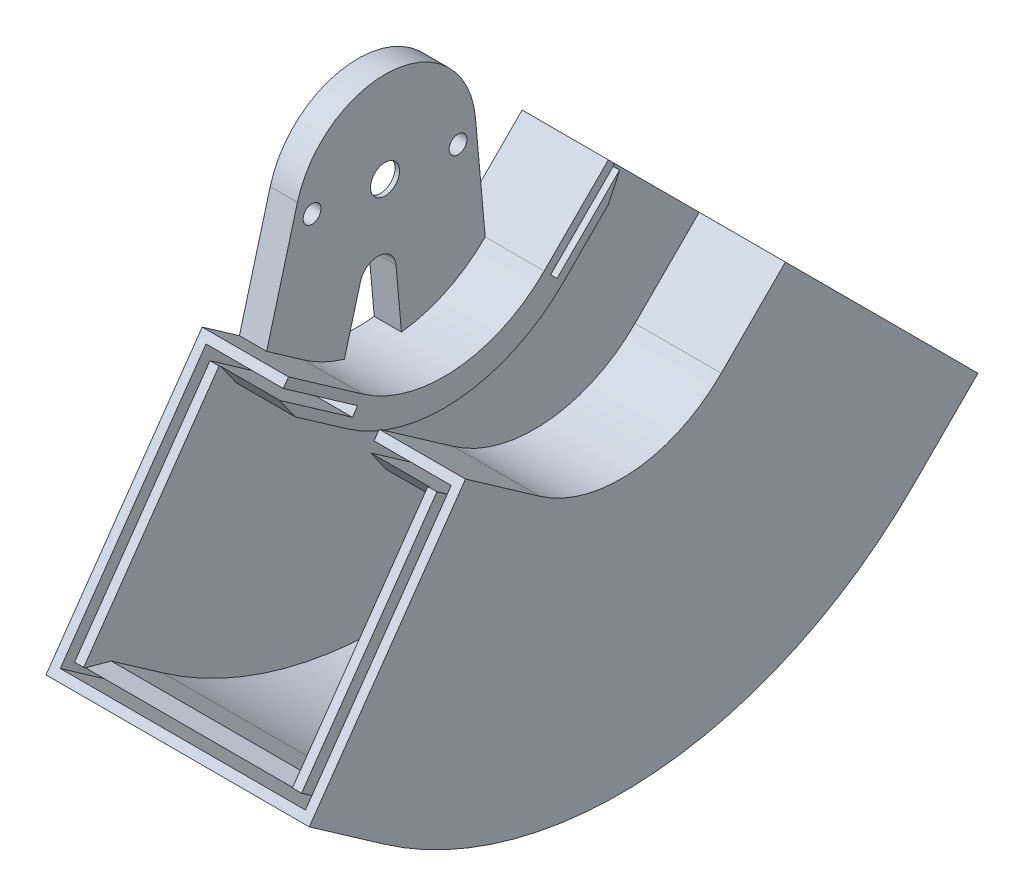
SolidWorks part; units mm, degrees
ref_plane "Front Plane" through (0, 0, 0) normal (0, 0, 1) x (1, 0, 0)
ref_plane "Top Plane" through (0, 0, 0) normal (0, 1, 0) x (1, 0, 0)
ref_plane "Right Plane" through (0, 0, 0) normal (1, 0, 0) x (0, 0, -1)
sketch "Sketch3" plane through (0, 0, 0) normal (1, 0, 0) x (0, 0, -1)
  line L0 (-22.7274, -32.4581) -> (-62.0633, -88.6355)
  line L1 (28.0184, -28.0184) -> (76.5118, -76.5118)
  line L2 (-22.7274, -32.4581) -> (0, 0) construction
  line L3 (0, 0) -> (28.0184, -28.0184) construction
  line L4 (0, 40.513) -> (0, -40.513) construction
  line L5 (-62.0633, -88.6355) -> (-66.4339, -94.8775)
  line L6 (76.5118, -76.5118) -> (81.8999, -81.8999)
  arc A2 (-62.0633, -88.6355) -> (76.5118, -76.5118) centre (0, 0) ccw
  arc A4 (-27.098, -38.7) -> (33.4066, -33.4066) centre (0, 0) ccw
  arc A5 (-22.7274, -32.4581) -> (28.0184, -28.0184) centre (0, 0) ccw
  arc A6 (-66.4339, -94.8775) -> (81.8999, -81.8999) centre (0, 0) ccw
  dimension "D1" = 216.408
  dimension "D2" = 135
  dimension "D3" = 94.488
  dimension "D4" = 7.62
  dimension "D6" = 7.62
  dimension "D5" = 80
extrude "Base extrude" add sketch "Sketch3" along normal blind 58.42 contours L5 A6 L6 A2 | A5 L0 A4 L1 region at (0, -39.9408, -3.4944) region at (0, -109.321, -9.5643)
sketch "Sketch4" plane through (58.42, 0, 0) normal (1, 0, 0) x (0, 0, -1)
  line L0 (-66.4339, -94.8775) -> (-22.7274, -32.4581)
  line L1 (28.0184, -28.0184) -> (81.8999, -81.8999)
  arc A0 (-22.7274, -32.4581) -> (28.0184, -28.0184) centre (0, 0) ccw
  arc A1 (-22.7274, -32.4581) -> (28.0184, -28.0184) centre (0, 0) ccw construction
  arc A2 (-66.4339, -94.8775) -> (81.8999, -81.8999) centre (0, 0) ccw
  arc A3 (-66.4339, -94.8775) -> (81.8999, -81.8999) centre (0, 0) ccw construction
  arc M1 (28.0184, -28.0184) -> (-22.7274, -32.4581) centre (0, 0) cw
  line M2 (-22.7274, -32.4581) -> (-27.098, -38.7)
  arc M3 (-27.098, -38.7) -> (33.4066, -33.4066) centre (0, 0) ccw
  line M4 (33.4066, -33.4066) -> (28.0184, -28.0184)
extrude "Outer wall" add sketch "Sketch4" along normal blind 7.62 contours L0 A2 L1 M3 | M4 M1 M2 M3 region at (58.42, -79.1939, -6.9286) region at (58.42, -39.9408, -3.4944)
ref_plane "Midplane" through (29.21, 0, 0) normal (-1, 0, 0) x (0, 0, 1)
mirror "Mirror1" about plane through (29.21, 0, 0) normal (-1, 0, 0) of "Outer wall"
sketch "Sketch6" plane through (0, 0, 0) normal (0, 0.5736, 0.8192) x (1, 0, 0)
  line L27 (-5.08, -42.164) -> (63.5, -42.164)
  line L28 (-5.08, -42.164) -> (-5.08, -113.284)
  line L29 (-5.08, -113.284) -> (63.5, -113.284)
  line L30 (63.5, -42.164) -> (63.5, -113.284)
  line L31 (-2.54, -44.704) -> (60.96, -44.704)
  line L32 (-2.54, -44.704) -> (-2.54, -110.744)
  line L33 (-2.54, -110.744) -> (60.96, -110.744)
  line L34 (60.96, -44.704) -> (60.96, -110.744)
  line L35 (58.42, -47.244) -> (0, -47.244) construction
  line L36 (0, -108.204) -> (0, -18.7894) construction
  line L37 (58.42, -18.7894) -> (58.42, -108.204) construction
  line L38 (58.42, -108.204) -> (0, -108.204) construction
  line L40 (0, -47.244) -> (58.42, -47.244)
  line L41 (0, -47.244) -> (0, -108.204)
  line L42 (0, -108.204) -> (58.42, -108.204)
  line L43 (58.42, -47.244) -> (58.42, -108.204)
  line L44 (-7.62, -39.624) -> (66.04, -39.624)
  line L45 (-7.62, -39.624) -> (-7.62, -115.824)
  line L46 (-7.62, -115.824) -> (66.04, -115.824)
  line L47 (66.04, -39.624) -> (66.04, -115.824)
  line M21 (-7.62, -39.624) -> (-7.62, -115.824)
  line M22 (-7.62, -115.824) -> (66.04, -115.824)
  line M23 (66.04, -115.824) -> (66.04, -39.624)
  line M24 (66.04, -39.624) -> (-7.62, -39.624)
  line M25 (58.42, -108.204) -> (0, -108.204)
  line M26 (0, -108.204) -> (0, -47.244)
  line M27 (0, -47.244) -> (58.42, -47.244)
  line M28 (58.42, -47.244) -> (58.42, -108.204)
  dimension "D1" = 2.54
  dimension "D2" = 2.54
  dimension "D3" = 2.54
  dimension "D4" = 2.54
  dimension "D5" = 2.54
  dimension "D6" = 2.54
  dimension "D7" = 2.54
  dimension "D8" = 2.54
extrude "Endcap 1" add sketch "Sketch6" along normal blind 25.4 contours L27 L30 L29 L28 M24 M21 M22 M23 | L34 L31 L32 L33 M28 M25 M26 M27 region at (29.21, -37.3698, 26.1667) region at (29.21, -33.3262, 23.3353)
sketch "Sketch7" plane through (0, 0, 0) normal (0, 0.7071, -0.7071) x (1, 0, 0)
  line L0 (-5.08, 113.284) -> (63.5, 113.284)
  line L1 (-5.08, 113.284) -> (-5.08, 42.164)
  line L2 (-5.08, 42.164) -> (63.5, 42.164)
  line L3 (63.5, 113.284) -> (63.5, 42.164)
  line L4 (-2.54, 110.744) -> (60.96, 110.744)
  line L5 (-2.54, 110.744) -> (-2.54, 44.704)
  line L6 (-2.54, 44.704) -> (60.96, 44.704)
  line L7 (60.96, 110.744) -> (60.96, 44.704)
  line L8 (0, 108.204) -> (58.42, 108.204)
  line L9 (0, 108.204) -> (0, 47.244)
  line L10 (0, 47.244) -> (58.42, 47.244)
  line L11 (58.42, 108.204) -> (58.42, 47.244)
  line L12 (-7.62, 115.824) -> (66.04, 115.824)
  line L13 (-7.62, 115.824) -> (-7.62, 39.624)
  line L14 (-7.62, 39.624) -> (66.04, 39.624)
  line L15 (66.04, 115.824) -> (66.04, 39.624)
  line L16 (58.42, 108.204) -> (0, 108.204) construction
  line L17 (58.42, 47.244) -> (58.42, 108.204) construction
  line L18 (66.04, 115.824) -> (-7.62, 115.824) construction
  line L19 (66.04, 39.624) -> (66.04, 115.824) construction
  line L20 (-7.62, 39.624) -> (-7.62, 115.824) construction
  line L21 (66.04, 39.624) -> (-7.62, 39.624) construction
  line M17 (66.04, 115.824) -> (-7.62, 115.824)
  line M18 (-7.62, 115.824) -> (-7.62, 39.624)
  line M19 (-7.62, 39.624) -> (66.04, 39.624)
  line M20 (66.04, 39.624) -> (66.04, 115.824)
  line M21 (0, 47.244) -> (0, 108.204)
  line M22 (0, 108.204) -> (58.42, 108.204)
  line M23 (58.42, 108.204) -> (58.42, 47.244)
  line M24 (58.42, 47.244) -> (0, 47.244)
  dimension "D1" = 2.54
  dimension "D2" = 2.54
  dimension "D3" = 2.54
  dimension "D4" = 2.54
  dimension "D5" = 2.54
  dimension "D6" = 2.54
  dimension "D7" = 2.54
  dimension "D8" = 2.54
extrude "Endcap 2" add sketch "Sketch7" along normal blind 25.4 contours L0 L3 L2 L1 M20 M17 M18 M19 | L7 L4 L5 L6 M24 M21 M22 M23 region at (29.21, -77.66, -77.66) region at (29.21, -81.1505, -81.1505)
chamfer "Internal Chamfer" distance 7.62 angle 20 4 edges at (29.21, -74.0667, 82.8697) (29.21, -24.1312, 47.9045) (29.21, -58.5513, -94.4723) (29.21, -15.446, -51.3671) first distance on face at (29.21, -81.3511, 72.4665) first distance on face at (29.21, -31.4156, 37.5013) first distance on face at (29.21, -67.5315, -85.492) first distance on face at (29.21, -24.4263, -42.3868)
ref_plane "Plane2" through (0, -13.9736, -1.2225) normal (0, -0.9962, -0.0872) x (-1, 0, 0)
sketch "Sketch10" plane through (0, -13.9736, -1.2225) normal (0, -0.9962, -0.0872) x (-1, 0, 0)
  line L0 (-66.04, 93.9078) -> (7.62, 93.9078) construction
  line L1 (-16.51, 95.5358) -> (-41.91, 95.5358)
  line L2 (-16.51, 95.5358) -> (-16.51, -82.1857)
  line L3 (-16.51, -82.1857) -> (-41.91, -82.1857)
  line L4 (-41.91, 95.5358) -> (-41.91, -82.1857)
  point P4 (-29.21, 93.9078)
  point P5 (-29.21, 95.5358)
  dimension "D1" = 25.4
extrude "Flywheel Hole" cut sketch "Sketch10" along normal up to next
sketch "Sketch11" plane through (-7.62, 0, 0) normal (-1, 0, 0) x (0, 0, 1)
  line L0 (-25.2982, 2.2719) -> (-28.0184, -28.0184)
  line L4 (-3.0636, -22.3183) -> (-4.5937, -39.3568)
  line L5 (6.8995, -21.445) -> (11.3704, -37.9575)
  line L6 (-20.4217, -1.79) -> (20.4217, 1.79) construction
  line L7 (24.5172, 6.6383) -> (33.1306, -25.1737)
  line L8 (43.5339, -17.8892) -> (22.7274, -32.4581) construction
  line L10 (1.5525, -17.7121) -> (-2.2178, 25.303) construction
  line L11 (22.7274, -32.4581) -> (43.5339, -17.8892)
  line L12 (22.7274, -32.4581) -> (33.1306, -25.1737)
  arc A1 (-28.0184, -28.0184) -> (22.7274, -32.4581) centre (0, 0) ccw construction
  circle A3 centre (0, 0) radius 4.064
  arc A4 (24.5172, 6.6383) -> (-25.2982, 2.2719) centre (0, 0) ccw
  circle A6 centre (-20.4217, -1.79) radius 2.5
  circle A7 centre (20.4217, 1.79) radius 2.5
  arc A8 (-3.0636, -22.3183) -> (6.8995, -21.445) centre (1.9961, -22.7727) cw
  arc A11 (11.3704, -37.9575) -> (22.7274, -32.4581) centre (0, 0) ccw
  arc A12 (-28.0184, -28.0184) -> (22.7274, -32.4581) centre (0, 0) ccw
  arc A13 (-28.0184, -28.0184) -> (-4.5937, -39.3568) centre (0, 0) ccw
  point P8 (-20.452, -1.4027)
  point P17 (0, 0)
  point P22 (0, 0)
  dimension "D3" = 8.128
  dimension "D2" = 25.4
  dimension "D1" = 5
  dimension "D5" = 5.08
  dimension "D4" = 41
  dimension "D7" = 43.18
  dimension "D6" = 0
extrude "Flywheel holder" add sketch "Sketch11" against normal blind 7.62
sketch "Sketch12" plane through (-7.62, 0, 0) normal (-1, 0, 0) x (0, 0, 1)
  circle A0 centre (0, 0) radius 14.605
  dimension "D1" = 29.21
extrude "Motor insert" cut sketch "Sketch12" against normal blind 6.35
